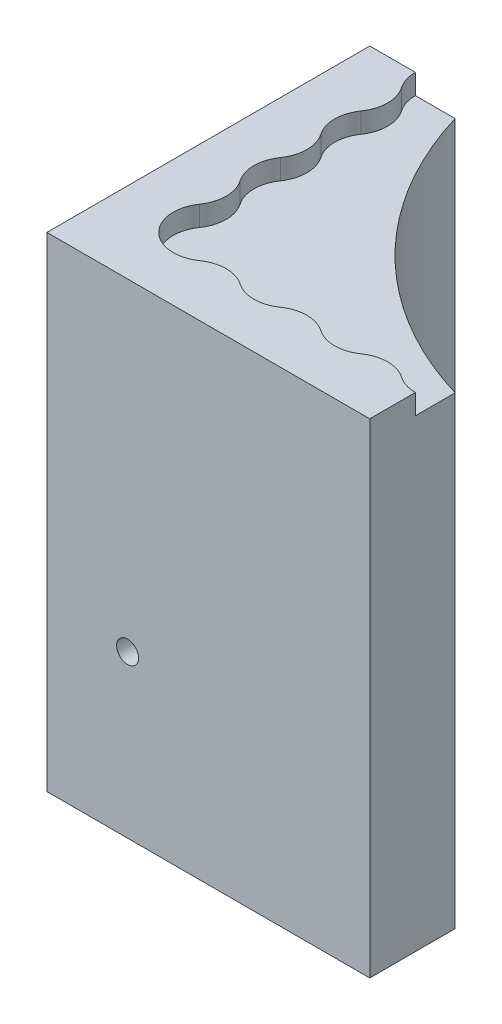
SolidWorks part; units mm, degrees
material "PET"
ref_plane "Front" through (0, 0, 0) normal (0, 0, 1) x (1, 0, 0)
ref_plane "Top" through (0, 0, 0) normal (0, 1, 0) x (1, 0, 0)
ref_plane "Right" through (0, 0, 0) normal (1, 0, 0) x (0, 0, -1)
sketch "Sketch1" plane through (0, 0, 0) normal (0, 1, 0) x (1, 0, 0)
  line L1 (0, 0) -> (50.8, 0)
  line L2 (0, 0) -> (0, 50.8)
  line L3 (0, 50.8) -> (50.8, 50.8)
  line L4 (50.8, 0) -> (50.8, 50.8)
  circle A0 centre (66.675, 66.675) radius 55.5625 construction
  dimension "D1" = 66.675
  dimension "D2" = 111.125
  dimension "D3" = 66.675
  dimension "D4" = 50.8
extrude "Boss-Extrude1" add sketch "Sketch1" along normal blind 76.2
sketch "Sketch2" plane through (0, 76.2, 0) normal (0, 1, 0) x (1, 0, 0)
  line L8 (129.2582, 124.9484) -> (133.499, 78.5045) construction
  line L9 (85.192, 137.4546) -> (125.4736, 129.1805) construction
  line L10 (129.2582, 124.9484) -> (133.499, 78.5045) construction
  line L11 (85.192, 137.4546) -> (125.4736, 129.1805) construction
  line L12 (130.017, 125.0177) -> (134.2578, 78.5738)
  line L13 (85.3453, 138.201) -> (125.6269, 129.9269)
  arc A0 (8.7916, 91.6214) -> (8.7916, 98.8786) centre (3.5805, 95.25) ccw construction
  arc A1 (8.7916, 91.6214) -> (8.7916, 86.1786) centre (12.7, 88.9) ccw construction
  arc A2 (8.7916, 78.9214) -> (8.7916, 86.1786) centre (3.5805, 82.55) ccw construction
  arc A3 (8.7916, 78.9214) -> (8.7796, 73.4959) centre (12.7, 76.2) ccw construction
  arc A4 (8.8014, 66.3169) -> (8.7796, 73.4959) centre (3.5524, 69.8905) ccw construction
  arc A5 (8.8014, 66.3169) -> (8.8053, 60.7032) centre (12.9199, 63.5129) ccw construction
  arc A6 (8.7834, 53.5096) -> (8.8053, 60.7032) centre (3.5613, 57.1223) ccw construction
  arc A7 (8.7834, 53.5096) -> (8.7916, 48.0786) centre (12.7, 50.8) ccw construction
  arc A8 (8.7916, 40.8214) -> (8.7916, 48.0786) centre (3.5805, 44.45) ccw construction
  arc A9 (8.7916, 40.8214) -> (8.7916, 35.3786) centre (12.7, 38.1) ccw construction
  arc A10 (8.7916, 28.1214) -> (8.7916, 35.3786) centre (3.5805, 31.75) ccw construction
  arc A11 (8.7916, 28.1214) -> (8.7916, 22.6786) centre (12.7, 25.4) ccw construction
  arc A12 (8.7916, 15.4214) -> (8.7916, 22.6786) centre (3.5805, 19.05) ccw construction
  arc A13 (8.7916, 15.4214) -> (15.4214, 8.7916) centre (12.7, 12.7) ccw construction
  arc A14 (22.6786, 8.7916) -> (15.4214, 8.7916) centre (19.05, 3.5805) ccw construction
  arc A15 (22.6786, 8.7916) -> (28.1214, 8.7916) centre (25.4, 12.7) ccw construction
  arc A16 (35.3786, 8.7916) -> (28.1214, 8.7916) centre (31.75, 3.5805) ccw construction
  arc A17 (35.3786, 8.7916) -> (40.8214, 8.7916) centre (38.1, 12.7) ccw construction
  arc A18 (48.0786, 8.7916) -> (40.8214, 8.7916) centre (44.45, 3.5805) ccw construction
  arc A19 (48.0786, 8.7916) -> (53.5096, 8.7834) centre (50.8, 12.7) ccw construction
  arc A20 (60.7032, 8.8053) -> (53.5096, 8.7834) centre (57.1223, 3.5613) ccw construction
  arc A21 (60.7032, 8.8053) -> (66.3169, 8.8014) centre (63.5129, 12.9199) ccw construction
  arc A22 (73.4959, 8.7796) -> (66.3169, 8.8014) centre (69.8905, 3.5524) ccw construction
  arc A23 (73.4959, 8.7796) -> (78.9214, 8.7916) centre (76.2, 12.7) ccw construction
  arc A24 (86.1786, 8.7916) -> (78.9214, 8.7916) centre (82.55, 3.5805) ccw construction
  arc A25 (86.1786, 8.7916) -> (91.6214, 8.7916) centre (88.9, 12.7) ccw construction
  arc A26 (98.8786, 8.7916) -> (91.6214, 8.7916) centre (95.25, 3.5805) ccw construction
  arc A27 (98.8786, 8.7916) -> (105.5642, 15.3394) centre (101.6, 12.7) ccw construction
  arc A28 (113.5841, 27.9306) -> (105.5642, 15.3394) centre (112.3572, 19.8624) ccw construction
  arc A29 (113.5841, 27.9306) -> (119.0625, 32.6538) centre (114.3, 32.639) ccw construction
  arc A30 (119.9168, 35.8549) -> (119.0625, 32.6538) centre (125.4124, 32.6736) ccw construction
  arc A31 (119.9168, 35.8549) -> (127.8227, 59.9277) centre (66.675, 66.675) ccw construction
  arc A32 (132.1466, 72.652) -> (127.8227, 59.9277) centre (158.75, 56.515) ccw construction
  arc A33 (132.1466, 72.652) -> (133.499, 78.5045) centre (123.9376, 77.6314) ccw construction
  arc A34 (129.2582, 124.9484) -> (125.4736, 129.1805) centre (124.5154, 124.5154) ccw construction
  arc A35 (85.192, 137.4546) -> (76.9535, 135.2891) centre (83.2602, 128.0498) ccw construction
  arc A36 (59.9277, 127.8227) -> (76.9535, 135.2891) centre (56.515, 158.75) ccw construction
  arc A37 (59.9277, 127.8227) -> (35.8549, 119.9168) centre (66.675, 66.675) ccw construction
  arc A38 (32.6538, 119.0625) -> (35.8549, 119.9168) centre (32.6736, 125.4124) ccw construction
  arc A39 (32.6538, 119.0625) -> (27.9306, 113.5841) centre (32.639, 114.3) ccw construction
  arc A40 (15.3394, 105.5642) -> (27.9306, 113.5841) centre (19.8624, 112.3572) ccw construction
  arc A41 (15.3394, 105.5642) -> (8.7916, 98.8786) centre (12.7, 101.6) ccw construction
  arc A42 (8.7916, 91.6214) -> (8.7916, 98.8786) centre (3.5805, 95.25) ccw construction
  arc A43 (8.7916, 91.6214) -> (8.7916, 86.1786) centre (12.7, 88.9) ccw construction
  arc A44 (8.7916, 78.9214) -> (8.7916, 86.1786) centre (3.5805, 82.55) ccw construction
  arc A45 (8.7916, 78.9214) -> (8.7796, 73.4959) centre (12.7, 76.2) ccw construction
  arc A46 (8.8014, 66.3169) -> (8.7796, 73.4959) centre (3.5524, 69.8905) ccw construction
  arc A47 (8.8014, 66.3169) -> (8.8053, 60.7032) centre (12.9199, 63.5129) ccw construction
  arc A48 (8.7834, 53.5096) -> (8.8053, 60.7032) centre (3.5613, 57.1223) ccw construction
  arc A49 (8.7834, 53.5096) -> (8.7916, 48.0786) centre (12.7, 50.8) ccw construction
  arc A50 (8.7916, 40.8214) -> (8.7916, 48.0786) centre (3.5805, 44.45) ccw construction
  arc A51 (8.7916, 40.8214) -> (8.7916, 35.3786) centre (12.7, 38.1) ccw construction
  arc A52 (8.7916, 28.1214) -> (8.7916, 35.3786) centre (3.5805, 31.75) ccw construction
  arc A53 (8.7916, 28.1214) -> (8.7916, 22.6786) centre (12.7, 25.4) ccw construction
  arc A54 (8.7916, 15.4214) -> (8.7916, 22.6786) centre (3.5805, 19.05) ccw construction
  arc A55 (8.7916, 15.4214) -> (15.4214, 8.7916) centre (12.7, 12.7) ccw construction
  arc A56 (22.6786, 8.7916) -> (15.4214, 8.7916) centre (19.05, 3.5805) ccw construction
  arc A57 (22.6786, 8.7916) -> (28.1214, 8.7916) centre (25.4, 12.7) ccw construction
  arc A58 (35.3786, 8.7916) -> (28.1214, 8.7916) centre (31.75, 3.5805) ccw construction
  arc A59 (35.3786, 8.7916) -> (40.8214, 8.7916) centre (38.1, 12.7) ccw construction
  arc A60 (48.0786, 8.7916) -> (40.8214, 8.7916) centre (44.45, 3.5805) ccw construction
  arc A61 (48.0786, 8.7916) -> (53.5096, 8.7834) centre (50.8, 12.7) ccw construction
  arc A62 (60.7032, 8.8053) -> (53.5096, 8.7834) centre (57.1223, 3.5613) ccw construction
  arc A63 (60.7032, 8.8053) -> (66.3169, 8.8014) centre (63.5129, 12.9199) ccw construction
  arc A64 (73.4959, 8.7796) -> (66.3169, 8.8014) centre (69.8905, 3.5524) ccw construction
  arc A65 (73.4959, 8.7796) -> (78.9214, 8.7916) centre (76.2, 12.7) ccw construction
  arc A66 (86.1786, 8.7916) -> (78.9214, 8.7916) centre (82.55, 3.5805) ccw construction
  arc A67 (86.1786, 8.7916) -> (91.6214, 8.7916) centre (88.9, 12.7) ccw construction
  arc A68 (98.8786, 8.7916) -> (91.6214, 8.7916) centre (95.25, 3.5805) ccw construction
  arc A69 (98.8786, 8.7916) -> (105.5642, 15.3394) centre (101.6, 12.7) ccw construction
  arc A70 (113.5841, 27.9306) -> (105.5642, 15.3394) centre (112.3572, 19.8624) ccw construction
  arc A71 (113.5841, 27.9306) -> (119.0625, 32.6538) centre (114.3, 32.639) ccw construction
  arc A72 (119.9168, 35.8549) -> (119.0625, 32.6538) centre (125.4124, 32.6736) ccw construction
  arc A73 (119.9168, 35.8549) -> (127.8227, 59.9277) centre (66.675, 66.675) ccw construction
  arc A74 (132.1466, 72.652) -> (127.8227, 59.9277) centre (158.75, 56.515) ccw construction
  arc A75 (132.1466, 72.652) -> (133.499, 78.5045) centre (123.9376, 77.6314) ccw construction
  arc A76 (129.2582, 124.9484) -> (125.4736, 129.1805) centre (124.5154, 124.5154) ccw construction
  arc A77 (85.192, 137.4546) -> (76.9535, 135.2891) centre (83.2602, 128.0498) ccw construction
  arc A78 (59.9277, 127.8227) -> (76.9535, 135.2891) centre (56.515, 158.75) ccw construction
  arc A79 (59.9277, 127.8227) -> (35.8549, 119.9168) centre (66.675, 66.675) ccw construction
  arc A80 (32.6538, 119.0625) -> (35.8549, 119.9168) centre (32.6736, 125.4124) ccw construction
  arc A81 (32.6538, 119.0625) -> (27.9306, 113.5841) centre (32.639, 114.3) ccw construction
  arc A82 (15.3394, 105.5642) -> (27.9306, 113.5841) centre (19.8624, 112.3572) ccw construction
  arc A83 (15.3394, 105.5642) -> (8.7916, 98.8786) centre (12.7, 101.6) ccw construction
  arc A84 (132.7981, 72.2568) -> (134.2578, 78.5738) centre (123.9376, 77.6314) ccw
  arc A85 (132.7981, 72.2568) -> (128.5801, 59.8441) centre (158.75, 56.515) ccw
  arc A86 (120.5763, 35.4731) -> (128.5801, 59.8441) centre (66.675, 66.675) ccw
  arc A87 (120.5763, 35.4731) -> (119.8245, 32.6562) centre (125.4124, 32.6736) ccw
  arc A88 (113.4695, 27.1773) -> (119.8245, 32.6562) centre (114.3, 32.639) ccw
  arc A89 (113.4695, 27.1773) -> (106.1985, 15.7617) centre (112.3572, 19.8624) ccw
  arc A90 (98.4431, 8.1663) -> (106.1985, 15.7617) centre (101.6, 12.7) ccw
  arc A91 (98.4431, 8.1663) -> (92.0569, 8.1663) centre (95.25, 3.5805) ccw
  arc A92 (85.7431, 8.1663) -> (92.0569, 8.1663) centre (88.9, 12.7) ccw
  arc A93 (85.7431, 8.1663) -> (79.3569, 8.1663) centre (82.55, 3.5805) ccw
  arc A94 (73.0633, 8.1523) -> (79.3569, 8.1663) centre (76.2, 12.7) ccw
  arc A95 (73.0633, 8.1523) -> (66.7457, 8.1715) centre (69.8905, 3.5524) ccw
  arc A96 (60.2735, 8.176) -> (66.7457, 8.1715) centre (63.5129, 12.9199) ccw
  arc A97 (60.2735, 8.176) -> (53.9431, 8.1568) centre (57.1223, 3.5613) ccw
  arc A98 (47.6431, 8.1663) -> (53.9431, 8.1568) centre (50.8, 12.7) ccw
  arc A99 (47.6431, 8.1663) -> (41.2569, 8.1663) centre (44.45, 3.5805) ccw
  arc A100 (34.9431, 8.1663) -> (41.2569, 8.1663) centre (38.1, 12.7) ccw
  arc A101 (34.9431, 8.1663) -> (28.5569, 8.1663) centre (31.75, 3.5805) ccw
  arc A102 (22.2431, 8.1663) -> (28.5569, 8.1663) centre (25.4, 12.7) ccw
  arc A103 (22.2431, 8.1663) -> (15.8569, 8.1663) centre (19.05, 3.5805) ccw
  arc A104 (8.1663, 15.8569) -> (15.8569, 8.1663) centre (12.7, 12.7) ccw
  arc A105 (8.1663, 15.8569) -> (8.1663, 22.2431) centre (3.5805, 19.05) ccw
  arc A106 (8.1663, 28.5569) -> (8.1663, 22.2431) centre (12.7, 25.4) ccw
  arc A107 (8.1663, 28.5569) -> (8.1663, 34.9431) centre (3.5805, 31.75) ccw
  arc A108 (8.1663, 41.2569) -> (8.1663, 34.9431) centre (12.7, 38.1) ccw
  arc A109 (8.1663, 41.2569) -> (8.1663, 47.6431) centre (3.5805, 44.45) ccw
  arc A110 (8.1568, 53.9431) -> (8.1663, 47.6431) centre (12.7, 50.8) ccw
  arc A111 (8.1568, 53.9431) -> (8.176, 60.2735) centre (3.5613, 57.1223) ccw
  arc A112 (8.1715, 66.7457) -> (8.176, 60.2735) centre (12.9199, 63.5129) ccw
  arc A113 (8.1715, 66.7457) -> (8.1523, 73.0633) centre (3.5524, 69.8905) ccw
  arc A114 (8.1663, 79.3569) -> (8.1523, 73.0633) centre (12.7, 76.2) ccw
  arc A115 (8.1663, 79.3569) -> (8.1663, 85.7431) centre (3.5805, 82.55) ccw
  arc A116 (8.1663, 92.0569) -> (8.1663, 85.7431) centre (12.7, 88.9) ccw
  arc A117 (8.1663, 92.0569) -> (8.1663, 98.4431) centre (3.5805, 95.25) ccw
  arc A118 (15.7617, 106.1985) -> (8.1663, 98.4431) centre (12.7, 101.6) ccw
  arc A119 (15.7617, 106.1985) -> (27.1773, 113.4695) centre (19.8624, 112.3572) ccw
  arc A120 (32.6562, 119.8245) -> (27.1773, 113.4695) centre (32.639, 114.3) ccw
  arc A121 (32.6562, 119.8245) -> (35.4731, 120.5763) centre (32.6736, 125.4124) ccw
  arc A122 (59.8441, 128.5801) -> (35.4731, 120.5763) centre (66.675, 66.675) ccw
  arc A123 (59.8441, 128.5801) -> (76.4529, 135.8637) centre (56.515, 158.75) ccw
  arc A124 (85.3453, 138.201) -> (76.4529, 135.8637) centre (83.2602, 128.0498) ccw
  arc A125 (130.017, 125.0177) -> (125.6269, 129.9269) centre (124.5154, 124.5154) ccw
  dimension "D1" = 0.762
extrude "Cut-Extrude1" cut sketch "Sketch2" against normal blind 3.175
sketch "Sketch3" plane through (0, 76.2, 0) normal (0, 1, 0) x (1, 0, 0)
  circle A0 centre (66.675, 66.675) radius 55.5625 construction
  circle A1 centre (66.675, 66.675) radius 55.5625
extrude "Cut-Extrude2" cut sketch "Sketch3" against normal through all
hole_wizard "#8-32 Tapped Hole1" positions "Sketch4" profile "Sketch5" tap size "#8-32" standard "ANSI Inch"
sketch "Sketch4" plane through (393.7, -15.875, 0) normal (0, 0, 1) x (1, 0, 0)
  point P30 (-381, 41.275)
  point P40 (-369.4274, 49.2196)
  point P41 (-381, 41.275)
sketch "Sketch5" plane through (12.7, 25.4, 0) normal (1, 0, 0) x (0, -1, 0)
  line L0 (0, 0) -> (0, 11.7464)
  line L1 (0, 11.7464) -> (1.7272, 10.7086)
  line L2 (1.7272, 10.7086) -> (1.7272, 0)
  line L3 (1.7272, 0) -> (0, 0)
  line L4 (0, 11.7464) -> (-1.7272, 10.7086) construction
  line L5 (0, -6.35) -> (0, 107.95) construction
  dimension "Tap Drill Dia." = 3.4544
  dimension "Tap Drill Depth" = 10.7086
  dimension "Drill Angle" = 118
hole_wizard "#8-32 Tapped Hole2" positions "Sketch6" profile "Sketch7" tap size "#8-32" standard "ANSI Inch"
sketch "Sketch6" plane through (0, -15.875, -393.7) normal (-1, 0, 0) x (0, 0, 1)
  point P36 (381, 41.275)
  point P38 (381, 41.275)
sketch "Sketch7" plane through (0, 25.4, -12.7) normal (0, 1, 0) x (0, 0, 1)
  line L0 (0, 0) -> (0, 11.7464)
  line L1 (0, 11.7464) -> (1.7272, 10.7086)
  line L2 (1.7272, 10.7086) -> (1.7272, 0)
  line L3 (1.7272, 0) -> (0, 0)
  line L4 (0, 11.7464) -> (-1.7272, 10.7086) construction
  line L5 (0, -6.35) -> (0, 107.95) construction
  dimension "Tap Drill Dia." = 3.4544
  dimension "Tap Drill Depth" = 10.7086
  dimension "Drill Angle" = 118
